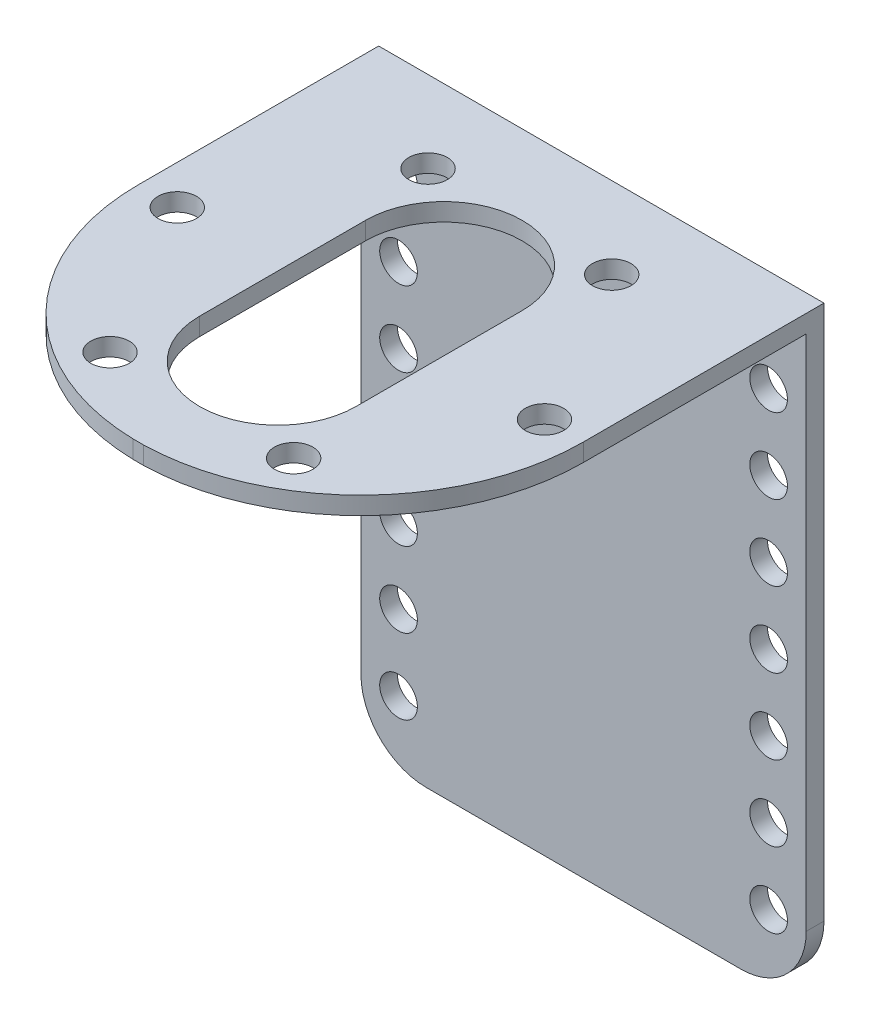
SolidWorks part; units mm, degrees
ref_plane "前视基准面" through (0, 0, 0) normal (0, 0, 1) x (1, 0, 0)
ref_plane "上视基准面" through (0, 0, 0) normal (0, 1, 0) x (1, 0, 0)
ref_plane "右视基准面" through (0, 0, 0) normal (1, 0, 0) x (0, 0, -1)
sketch "Sketch1" plane through (0, 0, 0) normal (0, 0, 1) x (1, 0, 0)
  line L0 (0, 24.6) -> (0, -4.1412) construction
  line L1 (13.275, -24.6) -> (-13.275, -24.6)
  line L2 (18.795, -19.08) -> (18.795, 24.6)
  line L3 (18.795, 24.6) -> (-18.795, 24.6)
  line L4 (-18.795, -19.08) -> (-18.795, 24.6)
  line L5 (18.795, -24.6) -> (-18.795, 24.6) construction
  line L6 (18.795, 24.6) -> (-18.795, -24.6) construction
  line L7 (-18.795, 24.6) -> (18.795, 24.6)
  line L8 (-18.795, 24.6) -> (-18.795, 26.1)
  line L9 (-18.795, 26.1) -> (18.795, 26.1)
  line L10 (18.795, 24.6) -> (18.795, 26.1)
  circle A0 centre (-15.62, 19.02) radius 1.59
  circle A1 centre (-15.62, 12.67) radius 1.59
  circle A2 centre (-15.62, 6.32) radius 1.59
  circle A3 centre (-15.62, -0.03) radius 1.59
  circle A4 centre (-15.62, -6.38) radius 1.59
  circle A5 centre (-15.62, -12.73) radius 1.59
  circle A6 centre (-15.62, -19.08) radius 1.59
  arc A7 (-13.275, -24.6) -> (-18.795, -19.08) centre (-13.275, -19.08) cw
  arc A8 (18.795, -19.08) -> (13.275, -24.6) centre (13.275, -19.08) cw
  circle A9 centre (15.62, -19.08) radius 1.59
  circle A10 centre (15.62, -12.73) radius 1.59
  circle A11 centre (15.62, -6.38) radius 1.59
  circle A12 centre (15.62, -0.03) radius 1.59
  circle A13 centre (15.62, 6.32) radius 1.59
  circle A14 centre (15.62, 12.67) radius 1.59
  circle A15 centre (15.62, 19.02) radius 1.59
  point P0 (0, 0)
  dimension "D8" = 3.18
  dimension "D9" = 3.18
  dimension "D10" = 3.18
  dimension "D11" = 3.18
  dimension "D12" = 3.18
  dimension "D13" = 3.18
  dimension "D14" = 3.18
  dimension "D15" = 5.52
  dimension "D16" = 5.52
  dimension "D2" = 6.35
  dimension "D3" = 6.35
  dimension "D4" = 6.35
  dimension "D5" = 6.35
  dimension "D6" = 6.35
  dimension "D7" = 6.35
  dimension "D17" = 49.2
  dimension "D18" = 37.59
  dimension "D19" = 7.08
  dimension "D20" = 15.62
extrude "Boss-Extrude1" add sketch "Sketch1" along normal blind 1.5 contours A8 L2 L3 L4 A7 L1 A14 A12 A10 A0 A1 A2 A3 A4 A5 A6 A9 A11 A13 A15 region at (0, 0.1791, 0)
extrude "Boss-Extrude2" add sketch "Sketch1<3>" along normal blind 39.09 contours L3 L10 L9 L8 region at (0, 25.35, 0)
sketch "Sketch1<3>" plane through (0, 0, 0) normal (0, 0, 1) x (1, 0, 0) same geometry as "Sketch1"
sketch "Sketch2" plane through (0, 26.1, 0) normal (0, 1, 0) x (1, 0, 0)
  line L0 (0, -20.3) -> (-15.5, -20.3) construction
  line L1 (0, -20.3) -> (-7.75, -6.8766) construction
  line L2 (-18.795, -39.09) -> (-18.795, 0) construction
  line L3 (18.795, -39.09) -> (18.795, 0) construction
  line L4 (6.605, -27.31) -> (6.605, -13.29)
  line L5 (-18.795, -20.3) -> (-18.795, -39.09)
  line L6 (-6.605, -27.31) -> (-6.605, -13.29)
  line L7 (6.605, -27.31) -> (-6.605, -13.29) construction
  line L8 (6.605, -13.29) -> (-6.605, -27.31) construction
  line L9 (-18.795, -39.09) -> (18.795, -39.09)
  line L10 (18.795, -39.09) -> (18.795, -20.3)
  circle A0 centre (0, -20.3) radius 15.5 construction
  circle A1 centre (-15.5, -20.3) radius 1.625
  circle A2 centre (-7.75, -6.8766) radius 1.625
  circle A3 centre (7.75, -6.8766) radius 1.625
  circle A4 centre (15.5, -20.3) radius 1.625
  circle A5 centre (7.75, -33.7234) radius 1.625
  circle A6 centre (-7.75, -33.7234) radius 1.625
  arc A7 (-6.605, -27.31) -> (6.605, -27.31) centre (0, -27.31) ccw
  arc A8 (-6.605, -13.29) -> (6.605, -13.29) centre (0, -13.29) cw
  arc A9 (-18.795, -20.3) -> (18.795, -20.3) centre (0, -20.3) ccw
  line M2 (-18.795, 0) -> (-18.795, -39.09)
  line M3 (-18.795, -39.09) -> (18.795, -39.09)
  line M4 (18.795, -39.09) -> (18.795, 0)
  dimension "D1" = 20.3
  dimension "D2" = 3.25
  dimension "D3" = 6
  dimension "D4" = 31
  dimension "D5" = 60
  dimension "D6" = 15.5
  dimension "D7" = 14.02
  dimension "D8" = 13.21
extrude "Cut-Extrude1" cut sketch "Sketch2" against normal blind 39.09 contours A2 | A3 | A8 L6 A7 L4 | A4 | A5 | A6 | A1 | A9 M2 M3 | A9 M3 M4 region at (0, 26.1, 20.3) region at (-14.603, 26.1, 34.8917) region at (14.603, 26.1, 34.8917) region at (-15.5, 26.1, 20.3) region at (-7.75, 26.1, 6.8766) region at (7.75, 26.1, 6.8766) region at (15.5, 26.1, 20.3) region at (7.75, 26.1, 33.7234) region at (-7.75, 26.1, 33.7234)
